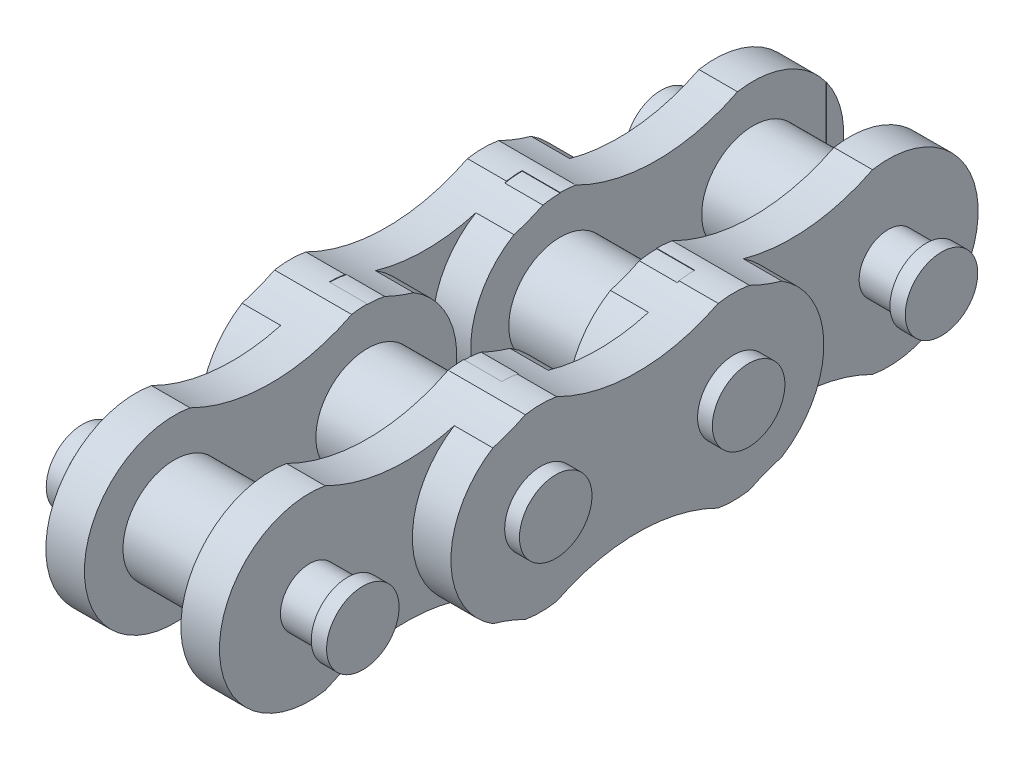
SolidWorks part; units mm, degrees
ref_plane "Front Plane" through (0, 0, 0) normal (0, 0, 1) x (1, 0, 0)
ref_plane "Top Plane"
ref_plane "Right Plane"
ref_plane "Plane1" through (0, 0, 0) normal (1, 0, 0) x (0, 0, -1)
sketch "Sketch1" plane through (0, 0, 0) normal (1, 0, 0) x (0, 0, -1)
  arc A0 (0.7719, 4.3775) -> (0.7719, -4.3775) centre (0, 0) ccw
  arc A1 (0.7719, -4.3775) -> (8.7531, -4.3775) centre (4.7625, -12.3215) cw
  arc A2 (8.7531, -4.3775) -> (10.2969, -4.3775) centre (9.525, 0) ccw
  arc A3 (10.2969, -4.3775) -> (18.2781, -4.3775) centre (14.2875, -12.3215) cw
  arc A4 (18.2781, -4.3775) -> (19.8219, -4.3775) centre (19.05, 0) ccw
  arc A5 (19.8219, -4.3775) -> (27.8031, -4.3775) centre (23.8125, -12.3215) cw
  arc A6 (27.8031, -4.3775) -> (27.8031, 4.3775) centre (28.575, 0) ccw
  arc A7 (27.8031, 4.3775) -> (19.8219, 4.3775) centre (23.8125, 12.3215) cw
  arc A8 (19.8219, 4.3775) -> (18.2781, 4.3775) centre (19.05, 0) ccw
  arc A9 (18.2781, 4.3775) -> (10.2969, 4.3775) centre (14.2875, 12.3215) cw
  arc A10 (10.2969, 4.3775) -> (8.7531, 4.3775) centre (9.525, 0) ccw
  arc A11 (8.7531, 4.3775) -> (0.7719, 4.3775) centre (4.7625, 12.3215) cw
extrude "Boss-Extrude1" add sketch "Sketch1" against normal blind 6.1913 and the other way blind 6.1913
ref_plane "Plane2" through (6.1913, 0, 0) normal (1, 0, 0) x (0, 0, -1)
sketch "Sketch2" plane through (6.1913, 0, 0) normal (1, 0, 0) x (0, 0, -1)
  line L0 (-8.89, -4.5466) -> (9.525, -4.5466)
  line L1 (9.525, -4.5466) -> (9.525, -4.445)
  line L2 (9.525, 4.445) -> (9.525, 4.5466)
  line L3 (9.525, 4.5466) -> (19.05, 4.5466)
  line L4 (19.05, 4.5466) -> (19.05, 4.445)
  line L5 (19.05, -4.445) -> (19.05, -4.5466)
  line L6 (19.05, -4.5466) -> (38.1, -4.5466)
  line L7 (38.1, -4.5466) -> (38.1, 13.4366)
  line L8 (38.1, 13.4366) -> (-8.89, 13.4366)
  line L9 (-8.89, 13.4366) -> (-8.89, -4.5466)
  arc A0 (9.525, -4.445) -> (9.525, 4.445) centre (9.525, 0) cw
  arc A1 (19.05, 4.445) -> (19.05, -4.445) centre (19.05, 0) cw
extrude "Cut-Extrude1" cut sketch "Sketch2" against normal blind 1.905 and the other way blind 1.905
ref_plane "Plane3" through (-6.1913, 0, 0) normal (-1, 0, 0) x (0, 0, 1)
sketch "Sketch3" plane through (-6.1913, 0, 0) normal (-1, 0, 0) x (0, 0, 1)
  line L0 (-38.1, -4.5466) -> (-19.05, -4.5466)
  line L1 (-19.05, -4.5466) -> (-19.05, -4.445)
  line L2 (-19.05, 4.445) -> (-19.05, 4.5466)
  line L3 (-19.05, 4.5466) -> (-9.525, 4.5466)
  line L4 (-9.525, 4.5466) -> (-9.525, 4.445)
  line L5 (-9.525, -4.445) -> (-9.525, -4.5466)
  line L6 (-9.525, -4.5466) -> (8.89, -4.5466)
  line L7 (8.89, -4.5466) -> (8.89, 13.4366)
  line L8 (8.89, 13.4366) -> (-38.1, 13.4366)
  line L9 (-38.1, 13.4366) -> (-38.1, -4.5466)
  arc A0 (-19.05, -4.445) -> (-19.05, 4.445) centre (-19.05, 0) cw
  arc A1 (-9.525, 4.445) -> (-9.525, -4.445) centre (-9.525, 0) cw
extrude "Cut-Extrude2" cut sketch "Sketch3" against normal blind 1.905 and the other way blind 1.905
ref_plane "Plane4" through (0, 0, 0) normal (1, 0, 0) x (0, 0, -1)
sketch "Sketch4" plane through (0, 0, 0) normal (1, 0, 0) x (0, 0, -1)
  line L0 (9.525, -4.4958) -> (19.05, -4.4958)
  line L1 (19.05, -4.4958) -> (19.05, -4.4196)
  line L2 (19.05, 4.4196) -> (19.05, 4.4958)
  line L3 (19.05, 4.4958) -> (9.525, 4.4958)
  line L4 (9.525, 4.4958) -> (9.525, 4.4196)
  line L5 (9.525, -4.4196) -> (9.525, -4.4958)
  arc A0 (19.05, -4.4196) -> (19.05, 4.4196) centre (19.05, 0) cw
  arc A1 (9.525, 4.4196) -> (9.525, -4.4196) centre (9.525, 0) cw
extrude "Cut-Extrude3" cut sketch "Sketch4" against normal blind 4.2609 and the other way blind 4.2609
ref_plane "Plane5" through (0, 0, 0) normal (1, 0, 0) x (0, 0, -1)
sketch "Sketch5" plane through (0, 0, 0) normal (1, 0, 0) x (0, 0, -1)
  line L0 (-8.89, -8.89) -> (32.1733, -8.89)
  line L1 (32.1733, -8.89) -> (32.1733, 8.89)
  line L2 (32.1733, 8.89) -> (-8.89, 8.89)
  line L3 (-8.89, 8.89) -> (-8.89, -8.89)
extrude "Cut-Extrude4" cut sketch "Sketch5" against normal blind 2.3813 and the other way blind 2.3813
ref_plane "Plane6" through (0, 0, 0) normal (0, 1, 0) x (1, 0, 0)
sketch "Sketch6" plane through (0, 0, 0) normal (0, 1, 0) x (1, 0, 0)
  line L0 (-6.9215, 0) -> (-6.9215, 1.7907)
  line L1 (-6.9215, 1.7907) -> (-6.1658, 1.7907)
  line L2 (-6.1658, 1.7907) -> (-6.1658, 1.4326)
  line L3 (-6.1658, 1.4326) -> (-2.4067, 1.4326)
  line L4 (-2.4067, 1.4326) -> (-2.4067, 2.54)
  line L5 (-2.4067, 2.54) -> (2.4067, 2.54)
  line L6 (2.4067, 2.54) -> (2.4067, 1.4326)
  line L7 (2.4067, 1.4326) -> (6.1658, 1.4326)
  line L8 (6.1658, 1.4326) -> (6.1658, 1.7907)
  line L9 (6.1658, 1.7907) -> (6.9215, 1.7907)
  line L10 (6.9215, 1.7907) -> (6.9215, 0)
  line L11 (6.9215, 0) -> (-6.9215, 0)
  line L12 (6.9215, 0) -> (-6.9215, 0) construction
revolve "Revolve1" add sketch "Sketch6" angle 360 about L12 reverse direction yes
ref_plane "Plane7" through (0, 0, 0) normal (1, 0, 0) x (0, 0, -1)
sketch "Sketch7" plane through (0, 0, 0) normal (1, 0, 0) x (0, 0, -1)
  line L0 (18.923, -8.89) -> (47.498, -8.89)
  line L1 (47.498, -8.89) -> (47.498, 8.89)
  line L2 (47.498, 8.89) -> (18.923, 8.89)
  line L3 (18.923, 8.89) -> (18.923, -8.89)
extrude "Cut-Extrude5" cut sketch "Sketch7" against normal blind 2.3559 and the other way blind 2.3559
ref_plane "Plane8" through (0, 0, 0) normal (0, 1, 0) x (1, 0, 0)
sketch "Sketch8" plane through (0, 0, 0) normal (0, 1, 0) x (1, 0, 0)
  line L0 (-6.9215, 28.575) -> (-6.9215, 30.3657)
  line L1 (-6.9215, 30.3657) -> (-6.1658, 30.3657)
  line L2 (-6.1658, 30.3657) -> (-6.1658, 30.0076)
  line L3 (-6.1658, 30.0076) -> (-2.4067, 30.0076)
  line L4 (-2.4067, 30.0076) -> (-2.4067, 31.115)
  line L5 (-2.4067, 31.115) -> (2.4067, 31.115)
  line L6 (2.4067, 31.115) -> (2.4067, 30.0076)
  line L7 (2.4067, 30.0076) -> (6.1658, 30.0076)
  line L8 (6.1658, 30.0076) -> (6.1658, 30.3657)
  line L9 (6.1658, 30.3657) -> (6.9215, 30.3657)
  line L10 (6.9215, 30.3657) -> (6.9215, 28.575)
  line L11 (6.9215, 28.575) -> (-6.9215, 28.575)
  line L12 (6.9215, 28.575) -> (-6.9215, 28.575) construction
revolve "Revolve2" add sketch "Sketch8" angle 360 about L12 reverse direction yes
ref_plane "Plane9" through (0, 0, 0) normal (0, 1, 0) x (1, 0, 0)
sketch "Sketch9" plane through (0, 0, 0) normal (0, 1, 0) x (1, 0, 0)
  line L0 (-6.9215, 19.05) -> (-6.9215, 20.8407)
  line L1 (-6.9215, 20.8407) -> (-6.1658, 20.8407)
  line L2 (-6.1658, 20.8407) -> (-6.1658, 20.4826)
  line L3 (-6.1658, 20.4826) -> (-2.4067, 20.4826)
  line L4 (-2.4067, 20.4826) -> (-2.4067, 21.59)
  line L5 (-2.4067, 21.59) -> (2.4067, 21.59)
  line L6 (2.4067, 21.59) -> (2.4067, 20.4826)
  line L7 (2.4067, 20.4826) -> (6.1658, 20.4826)
  line L8 (6.1658, 20.4826) -> (6.1658, 20.8407)
  line L9 (6.1658, 20.8407) -> (6.9215, 20.8407)
  line L10 (6.9215, 20.8407) -> (6.9215, 19.05)
  line L11 (6.9215, 19.05) -> (-6.9215, 19.05)
  line L12 (6.9215, 19.05) -> (-6.9215, 19.05) construction
revolve "Revolve3" add sketch "Sketch9" angle 360 about L12 reverse direction yes
ref_plane "Plane10" through (0, 0, 0) normal (0, 1, 0) x (1, 0, 0)
sketch "Sketch10" plane through (0, 0, 0) normal (0, 1, 0) x (1, 0, 0)
  line L0 (-6.9215, 9.525) -> (-6.9215, 11.3157)
  line L1 (-6.9215, 11.3157) -> (-6.1658, 11.3157)
  line L2 (-6.1658, 11.3157) -> (-6.1658, 10.9576)
  line L3 (-6.1658, 10.9576) -> (-2.4067, 10.9576)
  line L4 (-2.4067, 10.9576) -> (-2.4067, 12.065)
  line L5 (-2.4067, 12.065) -> (2.4067, 12.065)
  line L6 (2.4067, 12.065) -> (2.4067, 10.9576)
  line L7 (2.4067, 10.9576) -> (6.1658, 10.9576)
  line L8 (6.1658, 10.9576) -> (6.1658, 11.3157)
  line L9 (6.1658, 11.3157) -> (6.9215, 11.3157)
  line L10 (6.9215, 11.3157) -> (6.9215, 9.525)
  line L11 (6.9215, 9.525) -> (-6.9215, 9.525)
  line L12 (6.9215, 9.525) -> (-6.9215, 9.525) construction
revolve "Revolve4" add sketch "Sketch10" angle 360 about L12 reverse direction yes
